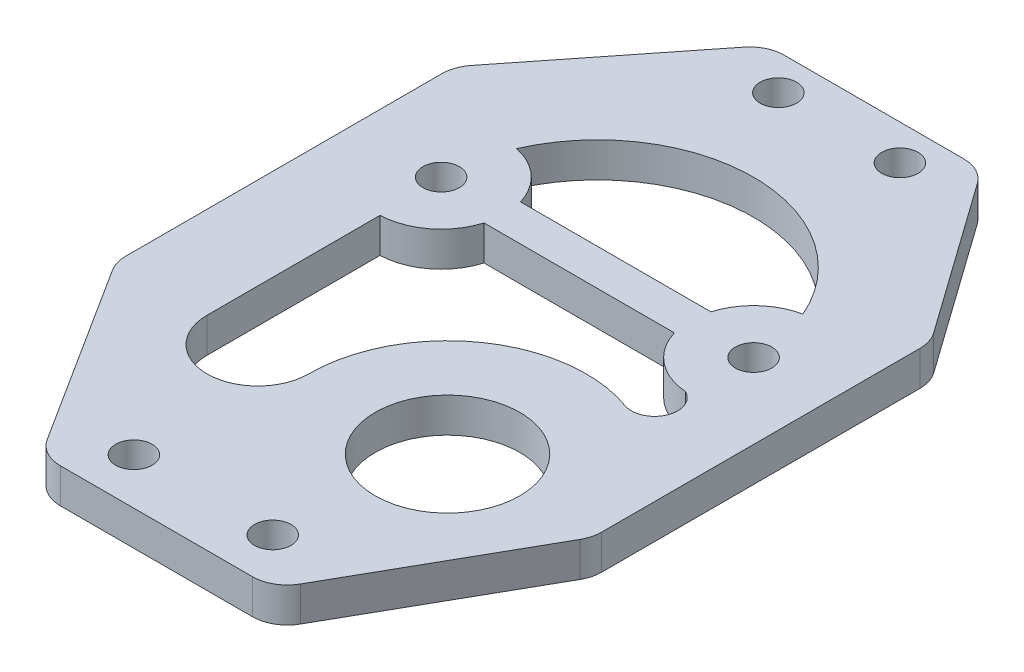
SolidWorks part; units mm, degrees
note: The reader was unsure of these and kept them because the rebuilt part matched: thickness of "Base-Flange1", "Sheet-Metal1", "Sac-Levha2".
ref_plane "Front Plane" through (0, 0, 0) normal (0, 0, 1) x (1, 0, 0)
ref_plane "Top Plane" through (0, 0, 0) normal (0, 1, 0) x (1, 0, 0)
ref_plane "Right Plane" through (0, 0, 0) normal (1, 0, 0) x (0, 0, -1)
sketch "Sketch1" plane through (0, 0, 0) normal (0, 1, 0) x (1, 0, 0)
  line L0 (0, 34.5262) -> (0, -34.5262) construction
  line L1 (-42.1133, 0) -> (42.1133, 0) construction
  line L2 (19.6094, -14.0594) -> (10.8621, -29.4802)
  line L3 (-7.7982, 31) -> (7.7021, 31)
  line L5 (-8.3526, -31) -> (8.2527, -31)
  line L6 (20, 14.9247) -> (20, -12.5792)
  line L7 (13.5, 7.05) -> (-13.5, 7.05) construction
  line L8 (10.147, 29.7386) -> (19.4449, 16.6633)
  line L9 (-13.2814, 0) -> (-13.2814, 1.547)
  line L10 (-8.2227, 8.625) -> (8.2303, 8.625)
  line L11 (-20.564, 16.7008) -> (-10.1508, 29.8615)
  line L12 (-21.2114, 14.8393) -> (-21.2114, -12.4977)
  line L13 (-13.2814, -13.4) -> (-13.2814, 0)
  line L14 (-20.7429, -14.1076) -> (-10.884, -29.6099)
  line L15 (-8.2227, 5.475) -> (8.2303, 5.475)
  circle A0 centre (7.5, -13.4) radius 6.25
  circle A1 centre (6, -27) radius 1.575
  circle A2 centre (-6, -27) radius 1.575
  arc A3 (11.6553, -2.1424) -> (13.1131, 1.5636) centre (12.21, -0.2209) ccw
  arc A4 (11.6553, -2.1424) -> (-4.5, -13.4) centre (7.5, -13.4) ccw
  arc A5 (-13.2814, -13.4) -> (-4.5, -13.4) centre (-8.8907, -13.4) ccw
  circle A6 centre (5.25, 27.9408) radius 1.575
  circle A7 centre (-5.25, 27.9408) radius 1.575
  circle A8 centre (13.5, 7.05) radius 1.575
  arc A9 (12.3796, 12.4347) -> (8.2303, 8.625) centre (13.5, 7.05) ccw
  arc A11 (12.3796, 12.4347) -> (-12.3766, 12.4416) centre (0, 7.05) ccw
  circle A12 centre (-13.5, 7.05) radius 1.575
  arc A13 (-13.2814, 1.547) -> (-8.2227, 5.475) centre (-13.5, 7.05) ccw
  arc A14 (-10.1508, 29.8615) -> (-7.7982, 31) centre (-7.7982, 28) cw
  arc A15 (-21.2114, -12.4977) -> (-20.7429, -14.1076) centre (-18.2114, -12.4977) ccw
  arc A16 (-21.2114, 14.8393) -> (-20.564, 16.7008) centre (-18.2114, 14.8393) cw
  arc A17 (-10.884, -29.6099) -> (-8.3526, -31) centre (-8.3526, -28) ccw
  arc A18 (10.8621, -29.4802) -> (8.2527, -31) centre (8.2527, -28) cw
  arc A19 (19.6094, -14.0594) -> (20, -12.5792) centre (17, -12.5792) ccw
  arc A20 (19.4449, 16.6633) -> (20, 14.9247) centre (17, 14.9247) cw
  arc A21 (10.147, 29.7386) -> (7.7021, 31) centre (7.7021, 28) ccw
  arc A22 (-8.2227, 8.625) -> (-12.3766, 12.4416) centre (-13.5, 7.05) ccw
  arc A23 (8.2303, 5.475) -> (13.1131, 1.5636) centre (13.5, 7.05) ccw
  point P0 (0, 0)
  point P4 (0, 0)
  point P8 (0, 0)
  point P36 (-9.25, 31)
  point P50 (-10, -31)
  point P53 (10, -31)
  point P56 (20, -13.3709)
  point P61 (9.25, 31)
  dimension "D2" = 17.6
  dimension "D4" = 12.5
  dimension "D5" = 4
  dimension "D9" = 62
  dimension "D10" = 20.45
  dimension "D12" = 13.15
  dimension "D14" = 4
  dimension "D15" = 12
  dimension "D16" = 10.5
  dimension "D18" = 3.15
  dimension "D19" = 13.5
  dimension "D20" = 11
  dimension "D22" = 4
  dimension "D24" = 3
  dimension "D25" = 3
  dimension "D26" = 3.15
  dimension "D3" = 7.5
  dimension "D6" = 4
  dimension "D7" = 6
  dimension "D8" = 12
  dimension "D11" = 4
  dimension "D13" = 4.71
  dimension "D17" = 5.25
  dimension "D21" = 7.93
  dimension "D23" = 6.5
base flange "Base-Flange1" sketch "Sketch1" thickness 3 reverse thickness direction yes parameters "D1"=0.7366
scale "Ölçek1" scale about centroid uniform scaling yes scale factor 2
sketch "Bend-Lines1" [suppressed] plane through (0, 0, 0) normal (0, 1, 0) x (1, 0, 0)
sketch "Bounding-Box1" [suppressed] plane through (0, 0, 0) normal (0, 1, 0) x (1, 0, 0)
sheet metal parameters "Sheet-Metal1" thickness 3 parameters "D1"=0.7366
flat pattern "Flat-Pattern1" [suppressed]
sketch "Bend-Lines2" plane through (0, 0, 0) normal (0, 1, 0) x (1, 0, 0)
sketch3d "Bounding-Box2" [suppressed]
  line L0 (13.4132, -59, 0) -> (13.4132, 3, 0) construction
  line L1 (-27.7982, -59, 0) -> (-27.7982, 3, 0) construction
  line L2 (13.4132, -59, 0) -> (-27.7982, -59, 0) construction
  line L3 (13.4132, 3, 0) -> (-27.7982, 3, 0) construction
sheet metal parameters "Sac-Levha2" thickness 3 parameters "D1"=0.7366
flat pattern "Flat-Pattern1"
sketch "Bend-Lines2" plane through (0, 0, 0) normal (0, 1, 0) x (1, 0, 0)
sketch3d "Bounding-Box2" [suppressed]
  line L0 (13.4132, -59, 0) -> (13.4132, 3, 0) construction
  line L1 (-27.7982, -59, 0) -> (-27.7982, 3, 0) construction
  line L2 (13.4132, -59, 0) -> (-27.7982, -59, 0) construction
  line L3 (13.4132, 3, 0) -> (-27.7982, 3, 0) construction
